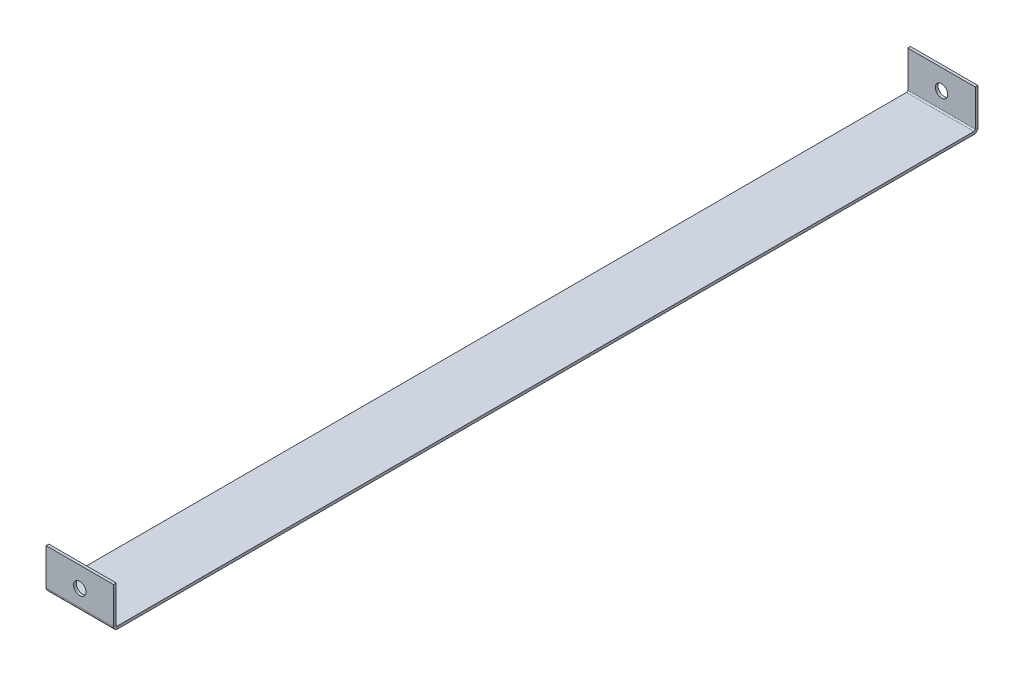
SolidWorks part; units mm, degrees
note: '?' marks a value the reader was unsure of. The reader was unsure of these and kept them because the rebuilt part matched: flange length of "Edge-Flange1".
material "AISI 304"
ref_plane "Front Plane" through (0, 0, 0) normal (0, 0, 1) x (1, 0, 0)
ref_plane "Top Plane" through (0, 0, 0) normal (0, 1, 0) x (1, 0, 0)
ref_plane "Right Plane" through (0, 0, 0) normal (1, 0, 0) x (0, 0, -1)
sketch "BaseFlange" plane through (0, 0, 0) normal (0, 1, 0) x (1, 0, 0)
  line L1 (25, -320) -> (-25, -320)
  line L2 (25, -320) -> (25, 320)
  line L3 (25, 320) -> (-25, 320)
  line L4 (-25, -320) -> (-25, 320)
  line L5 (25, -320) -> (-25, 320) construction
  line L6 (25, 320) -> (-25, -320) construction
  point P0 (0, 0)
  dimension "D1" = 50
  dimension "Length" = 640
sheet metal parameters "Sheet-Metal1" thickness 2 parameters "D1"=1
base flange "Base-Flange1" sketch "BaseFlange" thickness 2 reverse thickness direction yes parameters "D1"=1
edge flange "Edge-Flange1" sketch "Sketch6" flange profiles "Sketch6", "Sketch7" flange angle 90 flange length 30 flange position material inside bend radius 1 thickness 2 parameters "D6"=10, "D8"=1
sketch "Sketch6" plane through (0, 2, 320) normal (0, 0, 1) x (1, 0, 0)
  line L0 (-25, 0) -> (25, 0) construction
  line L1 (-25, 0) -> (25, 0)
  line L2 (-25, 0) -> (-25, 28)
  line L3 (-25, 28) -> (25, 28)
  line L4 (25, 28) -> (25, 0)
sketch "Sketch7" plane through (0, 2, -320) normal (0, 0, -1) x (-1, 0, 0)
  line L0 (-25, 0) -> (25, 0) construction
  line L1 (-25, 0) -> (25, 0)
  line L2 (-25, 0) -> (-25, 28)
  line L3 (-25, 28) -> (25, 28)
  line L4 (25, 28) -> (25, 0)
bend "EdgeBend1" bend radius 1 bend angle 90 parameters "D5"=1
bend "EdgeBend2" bend radius 1 bend angle 90 parameters "D5"=2
sketch "Sketch8" plane through (0, 0, 320) normal (0, 0, 1) x (1, 0, 0)
  line L2 (25, 30) -> (-25, 30) construction
  circle A0 centre (0, 15) radius 4.6
  dimension "D1" = 9.2
  dimension "D4" = 15
extrude "Extrude1" cut sketch "Sketch8" against normal through all normal cut yes
ref_axis "Axis1" through (0, 15, -320) along (0, 0, 1)?
flat pattern "Flat-Pattern1" [suppressed]
sketch "Bend-Lines1" plane through (0, 1.5, 0) normal (0, 1, 0) x (-1, 0, 0)
  point P0 (-260.4293, 642.4518)
  point P1 (260.4293, 642.4518)
  point P2 (260.4293, -642.4518)
  point P3 (-238.5, -642.4518)
  point P4 (283.4518, 619.4293)
  point P5 (283.4518, -619.4293)
  point P6 (-283.4518, 619.4293)
  point P7 (-283.4518, -611)
  point P8 (260.45, 620.1506)
  point P9 (-260.9293, 620.1506)
  point P10 (261.0591, -620.1506)
  point P11 (-238.5, -620.1506)
  point P12 (261.1506, 621.5)
  point P13 (261.1506, -620.25)
  point P14 (-261.1506, 619.9293)
  point P15 (-261.1506, -611)
bend of the flat pattern "Flatten-<EdgeBend1>1"
bend of the flat pattern "Flatten-<EdgeBend2>1"
